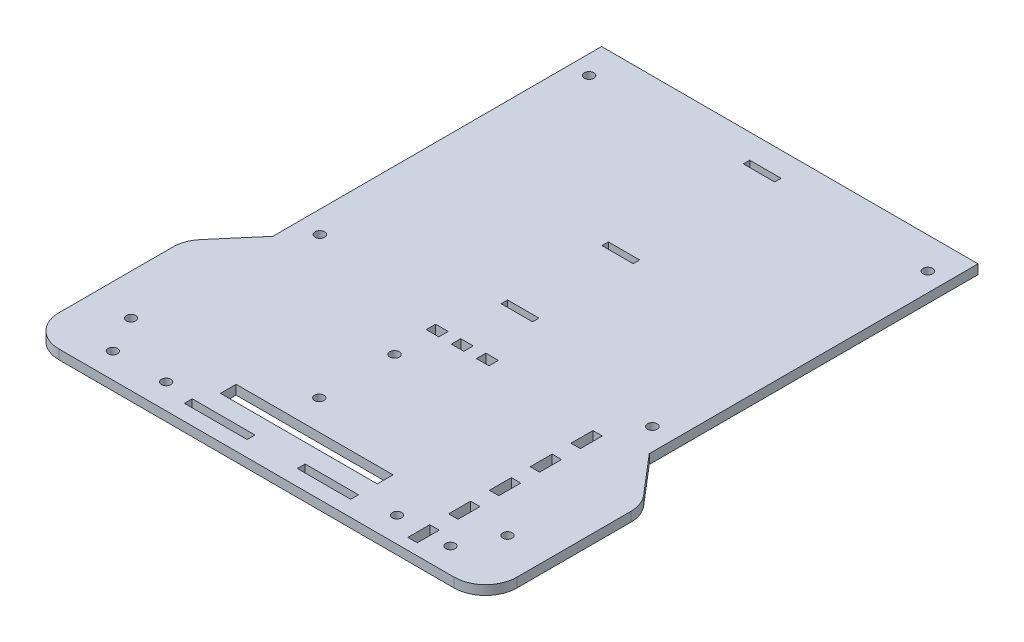
SolidWorks part; units mm, degrees
ref_plane "Front Plane" through (0, 0, 0) normal (0, 0, 1) x (1, 0, 0)
ref_plane "Top Plane" through (0, 0, 0) normal (0, 1, 0) x (1, 0, 0)
ref_plane "Right Plane" through (0, 0, 0) normal (1, 0, 0) x (0, 0, -1)
sketch "Sketch1" plane through (0, 0, 0) normal (0, 1, 0) x (1, 0, 0)
  line L0 (-73, -35) -> (-60, -19.8013)
  line L1 (60, -85) -> (-60, -85)
  line L2 (60, -19.8013) -> (60, 85)
  line L3 (60, 85) -> (-60, 85)
  line L4 (-60, -19.8013) -> (-60, 85)
  line L5 (60, -85) -> (-60, 85) construction
  line L6 (60, 85) -> (-60, -85) construction
  line L7 (0, 0) -> (0, -85) construction
  line L9 (-60, -85) -> (-73, -85)
  line L10 (-73, -35) -> (-73, -85)
  line L11 (60, -85) -> (73, -85)
  line L12 (73, -35) -> (73, -85)
  line L13 (73, -35) -> (60, -19.8013)
  point P0 (0, 0)
  dimension "D1" = 170
  dimension "D2" = 120
  dimension "D3" = 50
  dimension "D4" = 13
  dimension "D5" = 20
extrude "Boss-Extrude1" add sketch "Sketch1" along normal blind 3
sketch "Sketch2" plane through (0, 3, 0) normal (0, 1, 0) x (1, 0, 0)
  line L0 (0, 0) -> (0, 85) construction
  line L1 (60, 85) -> (-60, 85) construction
  line L2 (-60, 85) -> (-60, -19.8013) construction
  circle A0 centre (-53, -11.81) radius 1.525
  circle A1 centre (-54, 75) radius 1.525
  circle A2 centre (53, -11.81) radius 1.525
  circle A3 centre (54, 75) radius 1.525
  dimension "D1" = 10
  dimension "D2" = 3.05
  dimension "D3" = 6
  dimension "D4" = 3.05
  dimension "D5" = 7
  dimension "D6" = 86.81
extrude "Cut-Extrude1" cut sketch "Sketch2" against normal through all
sketch "Sketch3" plane through (0, 3, 0) normal (0, 1, 0) x (1, 0, 0)
  line L0 (-5, 32.14) -> (5, 32.14)
  line L1 (-5, 0.04) -> (5, 0.04)
  line L2 (-5, 0.04) -> (-5, -2.01)
  line L3 (-5, -2.01) -> (5, -2.01)
  line L4 (5, 0.04) -> (5, -2.01)
  line L5 (-5, 0.04) -> (5, -2.01) construction
  line L6 (-5, -2.01) -> (5, 0.04) construction
  line L7 (-5, 32.14) -> (-5, 30.09)
  line L8 (-5, 30.09) -> (5, 30.09)
  line L9 (5, 32.14) -> (5, 30.09)
  line L11 (-5, 77.24) -> (5, 77.24)
  line L12 (-5, 77.24) -> (-5, 75.19)
  line L13 (-5, 75.19) -> (5, 75.19)
  line L14 (-5, 64.24) -> (5, 64.24) [skipped]
  line L15 (-5, 64.24) -> (-5, 62.19) [skipped]
  line L16 (-5, 62.19) -> (5, 62.19) [skipped]
  line L17 (5, 64.24) -> (5, 62.19) [skipped]
  line L18 (5, 77.24) -> (5, 75.19)
  line L19 (-5, 77.24) -> (5, 75.19) construction
  line L20 (-5, 75.19) -> (5, 77.24) construction
  circle A0 centre (-53, -11.81) radius 1.525 construction
  point P0 (0, -0.985)
  point P8 (0, 76.215)
  dimension "D2" = 9.8
  dimension "D1" = 2.05
  dimension "D3" = 10
  dimension "D4" = 0
  dimension "D6" = 2.05
  dimension "D7" = 10
  dimension "D8" = 0
  dimension "D9" = 43.05
  dimension "D10" = 30.05
  dimension "D5" = 3
extrude "Cut-Extrude2" cut sketch "Sketch3" against normal through all
sketch "Sketch4" plane through (0, 3, 0) normal (0, 1, 0) x (1, 0, 0)
  line L0 (-73, -85) -> (73, -85) construction
  line L1 (-60, 85) -> (-60, -19.8013) construction
  line L2 (0, 0) -> (0, -85) construction
  circle A1 centre (-60, -65) radius 1.5
  circle A2 centre (-53.8153, -77) radius 1.5
  circle A3 centre (53.8153, -77) radius 1.5
  circle A4 centre (60, -65) radius 1.5
  dimension "D1" = 3
  dimension "D2" = 3
  dimension "D4" = 8
  dimension "D5" = 13.5
  dimension "D6" = 0
  dimension "D3" = 20
extrude "Cut-Extrude3" cut sketch "Sketch4" against normal blind 3
sketch "Sketch5" plane through (0, 3, 0) normal (0, 1, 0) x (1, 0, 0)
  line L0 (0, 0) -> (0, -85) construction
  line L2 (25, -71.5) -> (-25, -71.5)
  line L3 (25, -71.5) -> (25, -66.5)
  line L4 (25, -66.5) -> (-25, -66.5)
  line L5 (-25, -71.5) -> (-25, -66.5)
  line L6 (25, -71.5) -> (-25, -66.5) construction
  line L7 (-73, -85) -> (73, -85) construction
  line L8 (25, -66.5) -> (-25, -71.5) construction
  circle A0 centre (-36.8, -77) radius 1.5
  circle A1 centre (36.8, -77) radius 1.5
  point P0 (0, -69)
  dimension "D3" = 3
  dimension "D4" = 5.5
  dimension "D5" = 8
  dimension "D1" = 5
  dimension "D2" = 50
  dimension "D6" = 36.8
extrude "Cut-Extrude4" cut sketch "Sketch5" against normal blind 3
sketch "Sketch6" plane through (0, 3, 0) normal (0, 1, 0) x (1, 0, 0)
  line L0 (44.6365, -35.4032) -> (44.6365, -42.4032)
  line L7 (44.6365, -22.4032) -> (47.6365, -22.4032)
  line L8 (44.6365, -22.4032) -> (44.6365, -29.4032)
  line L9 (44.6365, -29.4032) -> (47.6365, -29.4032)
  line L10 (47.6365, -22.4032) -> (47.6365, -29.4032)
  line L11 (44.6365, -22.4032) -> (47.6365, -29.4032) construction
  line L12 (44.6365, -29.4032) -> (47.6365, -22.4032) construction
  line L13 (44.6365, -35.4032) -> (47.6365, -35.4032)
  line L14 (47.6365, -35.4032) -> (47.6365, -42.4032)
  line L15 (44.6365, -42.4032) -> (47.6365, -42.4032)
  line L16 (44.6365, -48.4032) -> (44.6365, -55.4032)
  line L17 (44.6365, -48.4032) -> (47.6365, -48.4032)
  line L18 (47.6365, -48.4032) -> (47.6365, -55.4032)
  line L19 (44.6365, -55.4032) -> (47.6365, -55.4032)
  line L20 (44.6365, -61.4032) -> (44.6365, -68.4032)
  line L21 (44.6365, -61.4032) -> (47.6365, -61.4032)
  line L22 (47.6365, -61.4032) -> (47.6365, -68.4032)
  line L23 (44.6365, -68.4032) -> (47.6365, -68.4032)
  line L24 (44.6365, -74.4032) -> (44.6365, -81.4032)
  line L25 (44.6365, -74.4032) -> (47.6365, -74.4032)
  line L26 (47.6365, -74.4032) -> (47.6365, -81.4032)
  line L27 (44.6365, -81.4032) -> (47.6365, -81.4032)
  line L29 (-9.793, -18.112) -> (-5.793, -18.112)
  line L30 (-9.793, -18.112) -> (-9.793, -21.112)
  line L31 (-9.793, -21.112) -> (-5.793, -21.112)
  line L32 (-5.793, -18.112) -> (-5.793, -21.112)
  line L33 (-9.793, -18.112) -> (-5.793, -21.112) construction
  line L34 (-9.793, -21.112) -> (-5.793, -18.112) construction
  line L35 (0.1365, -44.4032) -> (9.41, -44.4032) construction
  line L39 (-1.793, -18.1033) -> (2.207, -18.1033)
  line L40 (-1.793, -18.1033) -> (-1.793, -21.1033)
  line L41 (-1.793, -21.1033) -> (2.207, -21.1033)
  line L42 (2.207, -18.1033) -> (2.207, -21.1033)
  line L43 (-7.793, -19.612) -> (-7.793, -18.4227) construction
  line L44 (6.207, -18.1033) -> (10.207, -18.1033)
  line L45 (6.207, -18.1033) -> (6.207, -21.1033)
  line L46 (6.207, -21.1033) -> (10.207, -21.1033)
  line L47 (10.207, -18.1033) -> (10.207, -21.1033)
  point P0 (-7.793, -44.4032)
  point P9 (-7.793, -19.612)
  point P30 (-7.793, -44.4032)
  point P55 (-7.793, -44.4032)
extrude "Cut-Extrude5" cut sketch "Sketch6" against normal blind 10
sketch "Sketch7" plane through (0, 3, 0) normal (0, 1, 0) x (1, 0, 0)
  line L0 (-73, -35) -> (-73, -85) construction
  line L1 (-29.1759, -77.5) -> (-28, -77.5)
  line L2 (-73, -85) -> (73, -85) construction
  line L8 (0, -85) -> (0, -22.2641) construction
  line L9 (-8, -80) -> (-25, -80)
  line L10 (-8, -80) -> (-8, -77.5)
  line L11 (-8, -77.5) -> (-25, -77.5)
  line L16 (25, -80) -> (25, -77.5)
  line L17 (8, -80) -> (25, -80)
  line L18 (8, -80) -> (8, -77.5)
  line L19 (8, -77.5) -> (25, -77.5)
  line L21 (-25, -80) -> (-28, -80)
  line L23 (-25, -77.5) -> (-29.1759, -77.5)
  line L24 (-28, -80) -> (-28, -77.5)
  circle A0 centre (-68, -57) radius 1.5
  circle A1 centre (-8, -57) radius 1.5
  circle A2 centre (-8, -33) radius 1.5
  point P10 (-19, -78.75)
  dimension "D1" = 3
  dimension "D2" = 2.5
  dimension "D3" = 3
  dimension "D7" = 8
  dimension "D10" = 28
  dimension "D12" = 28
  dimension "D4" = 20
  dimension "D5" = 5
  dimension "D6" = 28
  dimension "D8" = 24
  dimension "D9" = 5
  dimension "D11" = 60
  dimension "D14" = 5
  dimension "D15" = 2.5
extrude "Cut-Extrude6" cut sketch "Sketch7" against normal blind 10 contours L24 L21 L9 L10 L11 L23 L1 | L19 L18 L17 L16 | A1 | A2 region at (-18, 3, 78.75) region at (16.5, 3, 78.75)
fillet "Fillet3" radius 10 4 edges at (-73, 1.5, 35) (73, 1.5, 35) (73, 1.5, 85) (-73, 1.5, 85)
fillet "Fillet2" radius 10 rebuild error yes
